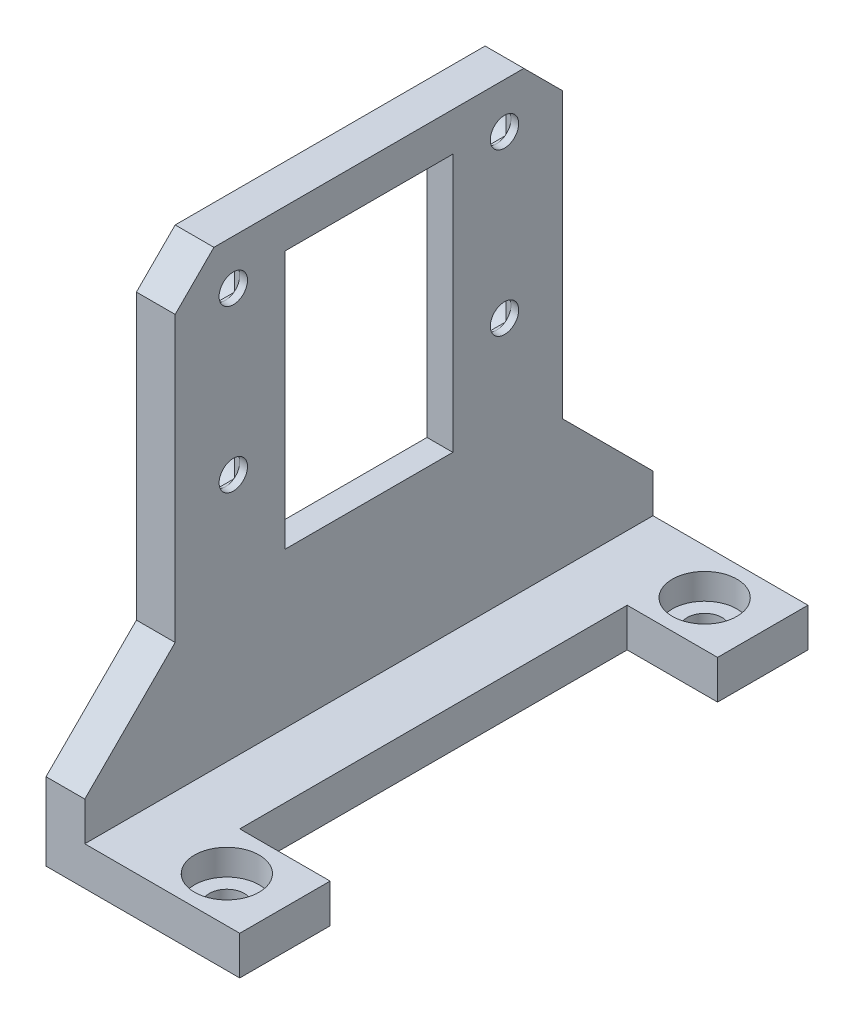
SolidWorks part; units mm, degrees
ref_plane "Front Plane" through (0, 0, 0) normal (0, 0, 1) x (1, 0, 0)
ref_plane "Top Plane" through (0, 0, 0) normal (0, 1, 0) x (1, 0, 0)
ref_plane "Right Plane" through (0, 0, 0) normal (1, 0, 0) x (0, 0, -1)
sketch "Sketch1" plane through (0, 0, 0) normal (0, 1, 0) x (1, 0, 0)
  line L0 (0, -22) -> (0, 22)
  line L1 (0, 22) -> (15, 22)
  line L2 (15, 22) -> (15, 15)
  line L3 (15, 15) -> (8, 15)
  line L4 (8, 15) -> (8, -15)
  line L5 (8, -15) -> (15, -15)
  line L6 (15, -15) -> (15, -22)
  line L7 (15, -22) -> (0, -22)
  point P4 (0, 0)
  dimension "D1" = 7
  dimension "D2" = 44
  dimension "D3" = 15
  dimension "D4" = 8
extrude "Boss-Extrude1" add sketch "Sketch1" along normal blind 3
sketch "Sketch2" plane through (0, 3, 0) normal (0, 1, 0) x (1, 0, 0)
  line L0 (10.5, -18.5) -> (10.5, 18.5) construction
  line L1 (15, 15) -> (15, 22) construction
  circle A0 centre (10.5, 18.5) radius 1.35
  circle A1 centre (10.5, -18.5) radius 1.35
  point P3 (10.5, 0)
  dimension "D1" = 2.7
  dimension "D2" = 37
  dimension "D3" = 4.5
extrude "Cut-Extrude1" cut sketch "Sketch2" against normal through all
sketch "Sketch3" plane through (0, 3, 0) normal (0, 1, 0) x (1, 0, 0)
  circle A0 centre (10.5, 18.5) radius 2.5
  circle A1 centre (10.5, -18.5) radius 2.5
  dimension "D1" = 5
extrude "Cut-Extrude2" cut sketch "Sketch3" against normal blind 2
sketch "Sketch4" plane through (0, 3, 0) normal (0, 1, 0) x (1, 0, 0)
  line L1 (0, 15) -> (3, 15)
  line L2 (0, 15) -> (0, -15)
  line L3 (0, -15) -> (3, -15)
  line L4 (3, 15) -> (3, -15)
  line L5 (0, 22) -> (0, -22) construction
  point P9 (3, 0)
  dimension "D1" = 3
  dimension "D2" = 30
extrude "Boss-Extrude2" add sketch "Sketch4" along normal blind 35
sketch "Sketch5" plane through (0, 0, 0) normal (-1, 0, 0) x (0, 0, 1)
  line L0 (-22, 0) -> (22, 0) construction
  line L1 (-10.5, 34.5) -> (10.5, 34.5) construction
  line L2 (-10.5, 34.5) -> (-10.5, 22) construction
  line L3 (-10.5, 22) -> (10.5, 22) construction
  line L4 (10.5, 34.5) -> (10.5, 22) construction
  circle A0 centre (-10.5, 34.5) radius 1.1
  circle A1 centre (10.5, 34.5) radius 1.1
  circle A2 centre (10.5, 22) radius 1.1
  circle A3 centre (-10.5, 22) radius 1.1
  point P4 (0, 22)
  dimension "D4" = 2.2
  dimension "D1" = 12.5
  dimension "D2" = 21
  dimension "15" = 22
extrude "Cut-Extrude3" cut sketch "Sketch5" against normal through all
sketch "Sketch6" plane through (0, 0, 0) normal (-1, 0, 0) x (0, 0, 1)
  line L0 (-22, 0) -> (22, 0) construction
  line L1 (-6.5, 15) -> (6.5, 15)
  line L2 (-6.5, 15) -> (-6.5, 35)
  line L3 (-6.5, 35) -> (6.5, 35)
  line L4 (6.5, 15) -> (6.5, 35)
  point P4 (0, 35)
  dimension "D1" = 13
  dimension "D2" = 20
  dimension "D3" = 15
extrude "Cut-Extrude4" cut sketch "Sketch6" against normal through all
chamfer "Chamfer1" distance 10 angle 45 2 edges at (1.5, 3, -15) (1.5, 3, 15)
chamfer "Chamfer2" distance 1 angle 45 4 edges at (0, 25, 6.5) (0, 35, 0) (0, 25, -6.5) (0, 15, 0)
chamfer "Chamfer3" distance 3 angle 45 2 edges at (1.5, 38, -15) (1.5, 38, 15)
sketch "Sketch7" plane through (0, 0, 0) normal (-1, 0, 0) x (0, 0, 1)
  circle A0 centre (-10.5, 34.5) radius 2
  circle A1 centre (10.5, 34.5) radius 2
  circle A2 centre (10.5, 22) radius 2
  circle A3 centre (-10.5, 22) radius 2
  dimension "D1" = 4
extrude "Cut-Extrude5" cut sketch "Sketch7" against normal blind 2
sketch "Sketch8" plane through (2, 0, 0) normal (-1, 0, 0) x (0, 0, 1)
  line L2 (-11.6, 32.8297) -> (-11.6, 36.1703)
  line L4 (-9.4, 32.8297) -> (-9.4, 36.1703)
  line L5 (-11.6, 32.8297) -> (-9.4, 36.1703) construction
  line L6 (-11.6, 36.1703) -> (-9.4, 32.8297) construction
  line L8 (-11.6, 20.3297) -> (-11.6, 23.6703)
  line L10 (-9.4, 20.3297) -> (-9.4, 23.6703)
  line L11 (-11.6, 20.3297) -> (-9.4, 23.6703) construction
  line L12 (-11.6, 23.6703) -> (-9.4, 20.3297) construction
  circle A0 centre (-10.5, 34.5) radius 2 construction
  circle A1 centre (-10.5, 22) radius 2 construction
  circle A2 centre (-10.5, 22) radius 1.1 construction
  circle A3 centre (-10.5, 34.5) radius 1.1 construction
  circle A4 centre (-10.5, 22) radius 2 construction
  arc A5 (-11.6, 20.3297) -> (-9.4, 20.3297) centre (-10.5, 22) ccw
  arc A6 (-11.6, 32.8297) -> (-9.4, 32.8297) centre (-10.5, 34.5) ccw
  arc A7 (-9.4, 36.1703) -> (-11.6, 36.1703) centre (-10.5, 34.5) ccw
  arc A8 (-9.4, 23.6703) -> (-11.6, 23.6703) centre (-10.5, 22) ccw
  point P0 (-10.5, 34.5)
  point P8 (-10.5, 22)
extrude "Cut-Extrude6" cut sketch "Sketch8" against normal blind 0.2
sketch "Sketch9" plane through (2.2, 0, 0) normal (-1, 0, 0) x (0, 0, 1)
  line L0 (-9.4, 22) -> (-9.4, 23.6703) construction
  line L1 (-11.6, 20.9) -> (-9.4, 20.9)
  line L2 (-11.6, 20.9) -> (-11.6, 23.1)
  line L3 (-11.6, 23.1) -> (-9.4, 23.1)
  line L4 (-9.4, 20.9) -> (-9.4, 23.1)
  line L5 (-11.6, 20.9) -> (-9.4, 23.1) construction
  line L6 (-11.6, 23.1) -> (-9.4, 20.9) construction
  line L7 (-9.4, 32.8297) -> (-9.4, 36.1703) construction
  line L8 (-11.6, 33.4) -> (-9.4, 33.4)
  line L9 (-11.6, 33.4) -> (-11.6, 35.6)
  line L10 (-11.6, 35.6) -> (-9.4, 35.6)
  line L11 (-9.4, 33.4) -> (-9.4, 35.6)
  line L12 (-11.6, 33.4) -> (-9.4, 35.6) construction
  line L13 (-11.6, 35.6) -> (-9.4, 33.4) construction
  point P0 (-10.5, 22)
  point P8 (-10.5, 34.5)
extrude "Cut-Extrude7" cut sketch "Sketch9" against normal blind 0.2
mirror "Mirror1" about plane through (0, 0, 0) normal (0, 0, 1) of "Cut-Extrude7", "Cut-Extrude6"
